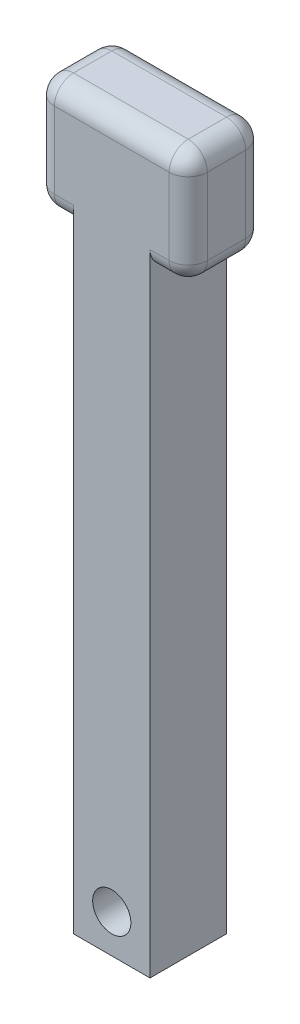
SolidWorks part; units mm, degrees
material "Miedź"
ref_plane "Front Plane" through (0, 0, 0) normal (0, 0, 1) x (1, 0, 0)
ref_plane "Top Plane" through (0, 0, 0) normal (0, 1, 0) x (1, 0, 0)
ref_plane "Right Plane" through (0, 0, 0) normal (1, 0, 0) x (0, 0, -1)
sketch "Szkic1" plane through (0, 0, 0) normal (0, 1, 0) x (1, 0, 0)
  line L1 (-0.5, -0.5) -> (0.5, -0.5)
  line L2 (-0.5, -0.5) -> (-0.5, 0.5)
  line L3 (-0.5, 0.5) -> (0.5, 0.5)
  line L4 (0.5, -0.5) -> (0.5, 0.5)
  line L5 (-0.5, -0.5) -> (0.5, 0.5) construction
  line L6 (-0.5, 0.5) -> (0.5, -0.5) construction
  point P0 (0, 0)
extrude "Dodanie-wyciągnięcie2" add sketch "Szkic1" along normal blind 9.5 contours L4 L3 L2 L1
sketch "Szkic2" plane through (0, 0, -0.5) normal (0, 0, -1) x (-1, 0, 0)
  line L0 (0, 0) -> (0, 0.5) construction
  line L1 (0.5, 0) -> (-0.5, 0) construction
  circle A0 centre (0, 0.5) radius 0.25
extrude "Wytnij-wyciągnięcie1" cut sketch "Szkic2" against normal blind 9.5
sketch "Szkic3" plane through (0.5, 0, 0) normal (1, 0, 0) x (0, 0, -1)
  line L0 (0.5, 9.5) -> (0.5, 0) construction
  line L1 (-0.5, 9.5) -> (0.5, 9.5)
  line L2 (-0.5, 9.5) -> (-0.5, 8)
  line L3 (-0.5, 8) -> (0.5, 8)
  line L4 (0.5, 9.5) -> (0.5, 8)
sketch "Szkic4" plane through (-0.5, 0, 0) normal (-1, 0, 0) x (0, 0, 1)
  line L0 (0.5, 9.5) -> (0.5, 0) construction
  line L1 (-0.5, 9.5) -> (0.5, 9.5)
  line L2 (-0.5, 9.5) -> (-0.5, 8.0016)
  line L3 (-0.5, 8.0016) -> (0.5, 8.0016)
  line L4 (0.5, 9.5) -> (0.5, 8.0016)
extrude "Dodanie-wyciągnięcie3" add sketch "Szkic3" along normal blind 0.5
extrude "Dodanie-wyciągnięcie4" add sketch "Szkic4" along normal blind 0.5
fillet "Zaokrąglenie1" radius 0.25 11 edges at (-1, 8.7508, 0.5) (-1, 8.7508, -0.5) (-1, 9.5, 0) (-0.75, 8.0016, -0.5) (0, 9.5, 0.5) (0, 9.5, -0.5) (1, 9.5, 0) (1, 8.75, -0.5) (1, 8.75, 0.5) (0.75, 8, 0.5) (0.75, 8, -0.5)
fillet "Zaokrąglenie2" radius 0.25 7 edges at (-0.9268, 8.0749, -0.4268) (-0.625, 8.0016, 0.5) (-0.9268, 8.0016, 0.4268) (0.9268, 8.0732, 0.4268) (0.9268, 8.0732, -0.4268) (-1, 8.0016, 0) (1, 8, 0)
